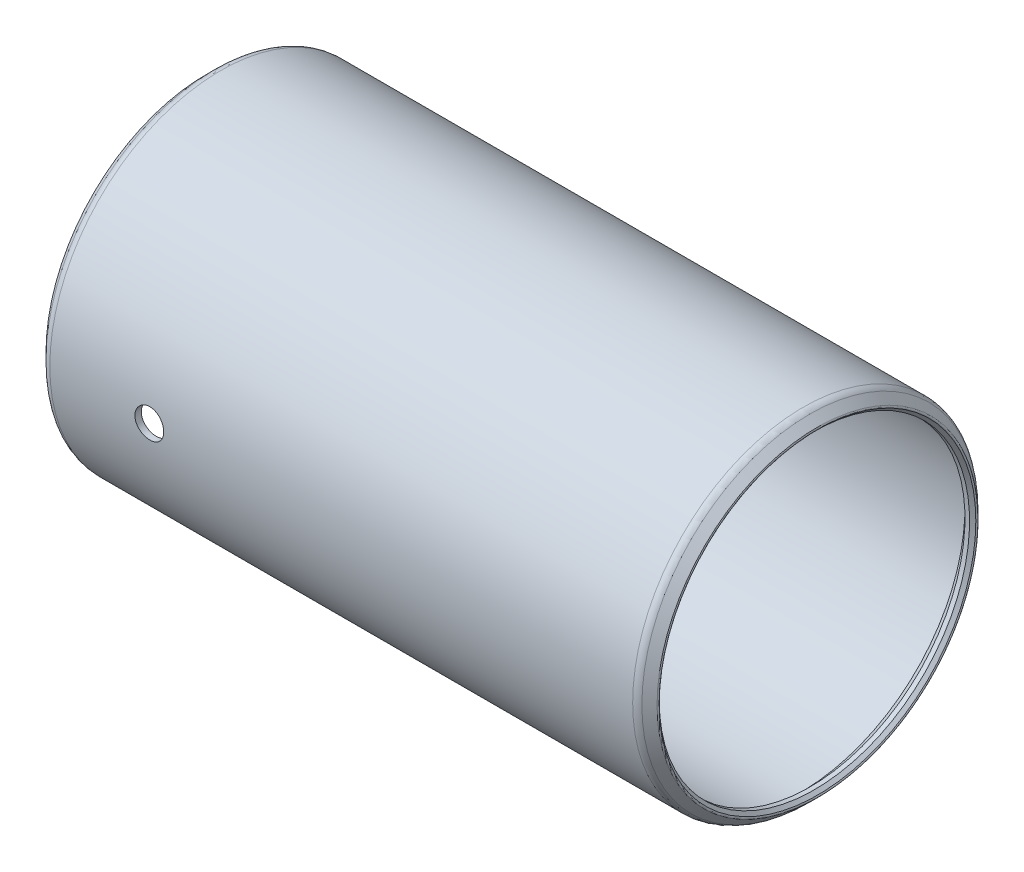
SolidWorks part; units mm, degrees
material "Cast Alloy Steel"
ref_plane "Front Plane" through (0, 0, 0) normal (0, 0, 1) x (1, 0, 0)
ref_plane "Top Plane" through (0, 0, 0) normal (0, 1, 0) x (1, 0, 0)
ref_plane "Right Plane" through (0, 0, 0) normal (1, 0, 0) x (0, 0, -1)
ref_plane "Plane1" through (49.3014, 0, 0) normal (1, 0, 0) x (0, 0, -1)
sketch "Sketch1" plane through (0, 0, 0) normal (0, 0, 1) x (1, 0, 0)
  line L0 (-0.6395, 13.1046) -> (-0.381, 12.846)
  line L1 (-0.381, 12.846) -> (0, 12.846)
  line L2 (0, 12.846) -> (0.762, 13.6081)
  line L3 (0.762, 13.6081) -> (48.5394, 13.6081)
  line L4 (48.5394, 13.6081) -> (49.3014, 12.846)
  line L5 (49.3014, 12.846) -> (49.6824, 12.846)
  line L6 (49.6824, 12.846) -> (49.9409, 13.1046)
  line L7 (49.9409, 13.2842) -> (49.3132, 13.9119)
  line L8 (48.7744, 14.1351) -> (0.527, 14.1351)
  line L9 (-0.0118, 13.9119) -> (-0.6395, 13.2842)
  line L10 (49.3014, 0) -> (0, 0) construction
  arc A0 (-0.6395, 13.2842) -> (-0.6395, 13.1046) centre (-0.5497, 13.1944) ccw
  arc A1 (49.9409, 13.1046) -> (49.9409, 13.2842) centre (49.8511, 13.1944) ccw
  arc A2 (49.3132, 13.9119) -> (48.7744, 14.1351) centre (48.7744, 13.3731) ccw
  arc A3 (0.527, 14.1351) -> (-0.0118, 13.9119) centre (0.527, 13.3731) ccw
revolve "Revolve1" add sketch "Sketch1" angle 360 about L10 reverse direction yes
sketch "Sketch2" plane through (0, 0, 0) normal (0, 0, 1) x (1, 0, 0)
  circle A0 centre (8.763, 0) radius 1.1938
extrude "Cut-Extrude1" cut sketch "Sketch2" along normal blind 14.1351
ref_plane "Plane2" through (24.6507, 0, 0) normal (1, 0, 0) x (0, 0, -1)
ref_plane "cp1 XY" through (24.6507, 0, 0) normal (1, 0, 0) x (0, 0, -1)
ref_plane "cp1 XZ" through (0, 14.1351, 0) normal (0, -1, 0) x (-1, 0, 0)
ref_plane "cp1 YZ" through (0, 0, 0) normal (0, 0, -1) x (-1, 0, 0)
ref_axis "cp1 X" through (24.6507, 14.1351, 80.9) along (0, 0, -1)
ref_axis "cp1 Y" through (24.6507, -50, 0) along (0, 1, 0)
ref_axis "cp1 Z" through (80.9, 14.1351, 0) along (-1, 0, 0)
sketch3d "cp1"
  point P0 (24.6507, 14.1351, 0)
ref_plane "cp2 XY" through (24.6507, 0, 0) normal (1, 0, 0) x (0, 0, -1)
ref_plane "cp2 XZ" through (0, 0, 0) normal (0, -1, 0) x (-1, 0, 0)
ref_plane "cp2 YZ" through (0, 0, -14.1351) normal (0, 0, -1) x (-1, 0, 0)
ref_axis "cp2 X" through (24.6507, 0, 80.9) along (0, 0, -1)
ref_axis "cp2 Y" through (24.6507, -50, -14.1351) along (0, 1, 0)
ref_axis "cp2 Z" through (80.9, 0, -14.1351) along (-1, 0, 0)
sketch3d "cp2"
  point P0 (24.6507, 0, -14.1351)
ref_plane "cp3 XY" through (24.6507, 0, 0) normal (1, 0, 0) x (0, 0, -1)
ref_plane "cp3 XZ" through (0, -14.1351, 0) normal (0, -1, 0) x (-1, 0, 0)
ref_plane "cp3 YZ" through (0, 0, 0) normal (0, 0, -1) x (-1, 0, 0)
ref_axis "cp3 X" through (24.6507, -14.1351, 80.9) along (0, 0, -1)
ref_axis "cp3 Y" through (24.6507, -50, 0) along (0, 1, 0)
ref_axis "cp3 Z" through (80.9, -14.1351, 0) along (-1, 0, 0)
sketch3d "cp3"
  point P0 (24.6507, -14.1351, 0)
ref_plane "cp4 XY" through (24.6507, 0, 0) normal (1, 0, 0) x (0, 0, -1)
ref_plane "cp4 XZ" through (0, 0, 0) normal (0, -1, 0) x (-1, 0, 0)
ref_plane "cp4 YZ" through (0, 0, 14.1351) normal (0, 0, -1) x (-1, 0, 0)
ref_axis "cp4 X" through (24.6507, 0, 80.9) along (0, 0, -1)
ref_axis "cp4 Y" through (24.6507, -50, 14.1351) along (0, 1, 0)
ref_axis "cp4 Z" through (80.9, 0, 14.1351) along (-1, 0, 0)
sketch3d "cp4"
  point P0 (24.6507, 0, 14.1351)
ref_plane "tube_front XY" through (0, 0, 0) normal (1, 0, 0) x (0, 0, -1)
ref_plane "tube_front XZ" through (0, 0, 0) normal (0, -1, 0) x (-1, 0, 0)
ref_plane "tube_front YZ" through (0, 0, 0) normal (0, 0, -1) x (-1, 0, 0)
ref_axis "tube_front X" through (0, 0, 80.9) along (0, 0, -1)
ref_axis "tube_front Y" through (0, -50, 0) along (0, 1, 0)
ref_axis "tube_front Z" through (80.9, 0, 0) along (-1, 0, 0)
sketch3d "tube_front"
  point P0 (0, 0, 0)
ref_plane "tube_rear XY" through (49.3014, 0, 0) normal (1, 0, 0) x (0, 0, -1)
ref_plane "tube_rear XZ" through (0, 0, 0) normal (0, -1, 0) x (-1, 0, 0)
ref_plane "tube_rear YZ" through (0, 0, 0) normal (0, 0, -1) x (-1, 0, 0)
ref_axis "tube_rear X" through (49.3014, 0, 80.9) along (0, 0, -1)
ref_axis "tube_rear Y" through (49.3014, -50, 0) along (0, 1, 0)
ref_axis "tube_rear Z" through (80.9, 0, 0) along (-1, 0, 0)
sketch3d "tube_rear"
  point P0 (49.3014, 0, 0)
